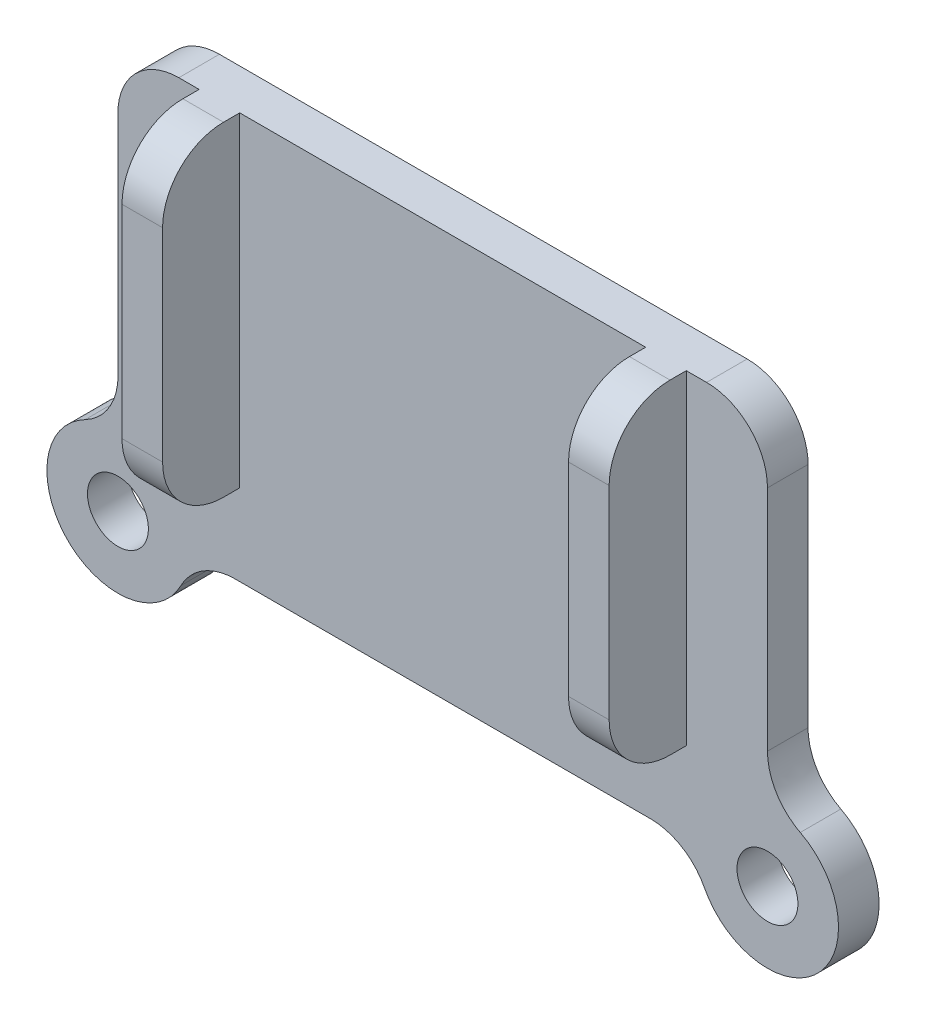
SolidWorks part; units mm, degrees
ref_plane "前基準面" through (0, 0, 0) normal (0, 0, 1) x (1, 0, 0)
ref_plane "上基準面" through (0, 0, 0) normal (0, 1, 0) x (1, 0, 0)
ref_plane "右基準面" through (0, 0, 0) normal (1, 0, 0) x (0, 0, -1)
sketch "草圖1" plane through (0, 0, 0) normal (0, 0, 1) x (1, 0, 0)
  line L1 (-16, -10) -> (16, -10)
  line L2 (-16, -10) -> (-16, 10)
  line L3 (-16, 10) -> (16, 10)
  line L4 (16, -10) -> (16, 10)
  line L5 (-16, -10) -> (16, 10) construction
  line L6 (-16, 10) -> (16, -10) construction
  point P0 (0, 0)
  dimension "D1" = 20
  dimension "D2" = 32
extrude "填料-伸長1" add sketch "草圖1" along normal blind 2
sketch "草圖2" plane through (0, 0, 0) normal (0, 0, -1) x (-1, 0, 0)
  circle A0 centre (-16, -10) radius 3.5
  dimension "D1" = 7
extrude "填料-伸長2" add sketch "草圖2" against normal up to surface (2 mm away) up to face at (0, 0, 2)
hole_wizard "Ø3.0 (3) 直徑孔1" positions "草圖3" profile "草圖4" hole size "Ø3.0" standard "ISO" end condition through all
sketch "草圖3" plane through (0, 0, 0) normal (0, 0, -1) x (-1, 0, 0)
  point P0 (-16, -10)
sketch "草圖4" plane through (16, -10, 0) normal (1, 0, 0) x (0, 1, 0)
  line L0 (0, 0) -> (0, 2)
  line L1 (0, 2) -> (1.5, 2)
  line L2 (1.5, 2) -> (1.5, 0)
  line L5 (1.5, 0) -> (0, 0)
  line L11 (0, -6.35) -> (0, 107.95) construction
  dimension "貫穿孔直徑" = 3
  dimension "貫穿孔深度" = 2
mirror "鏡射1" about plane through (0, 0, 0) normal (1, 0, 0) of "Ø3.0 (3) 直徑孔1", "填料-伸長2"
sketch "草圖5" plane through (0, 0, 2) normal (0, 0, 1) x (1, 0, 0)
  line L0 (-16, 10) -> (-16, -6.5) construction
  line L1 (-12, -6) -> (-10, -6)
  line L2 (-12, -6) -> (-12, 10)
  line L3 (-12, 10) -> (-10, 10)
  line L4 (-10, -6) -> (-10, 10)
  line L5 (-12, -6) -> (-10, 10) construction
  line L6 (-12, 10) -> (-10, -6) construction
  line L7 (16, 10) -> (-16, 10) construction
  line L8 (-12.5, -10) -> (12.5, -10) construction
  point P0 (-11, 2)
  dimension "D1" = 6
  dimension "D2" = 4
  dimension "D3" = 4
extrude "填料-伸長3" add sketch "草圖5" along normal blind 3.8
mirror "鏡射2" about plane through (0, 0, 0) normal (1, 0, 0) of "填料-伸長3"
fillet "圓角1" radius 3 10 edges at (-16, -6.5, 1) (-12.5, -10, 1) (12.5, -10, 1) (16, 10, 1) (16, -6.5, 1) (11, 10, 5.8) (11, -6, 5.8) (-16, 10, 1) (-11, 10, 5.8) (-11, -6, 5.8) first distance on face at (-16.3624, -10.3624, 1) first distance on face at (16.3624, -10.3624, 1) first distance on face at (0, 10, 2.9333) first distance on face at (11, -6, 3.9) first distance on face at (-11, -6, 3.9)
